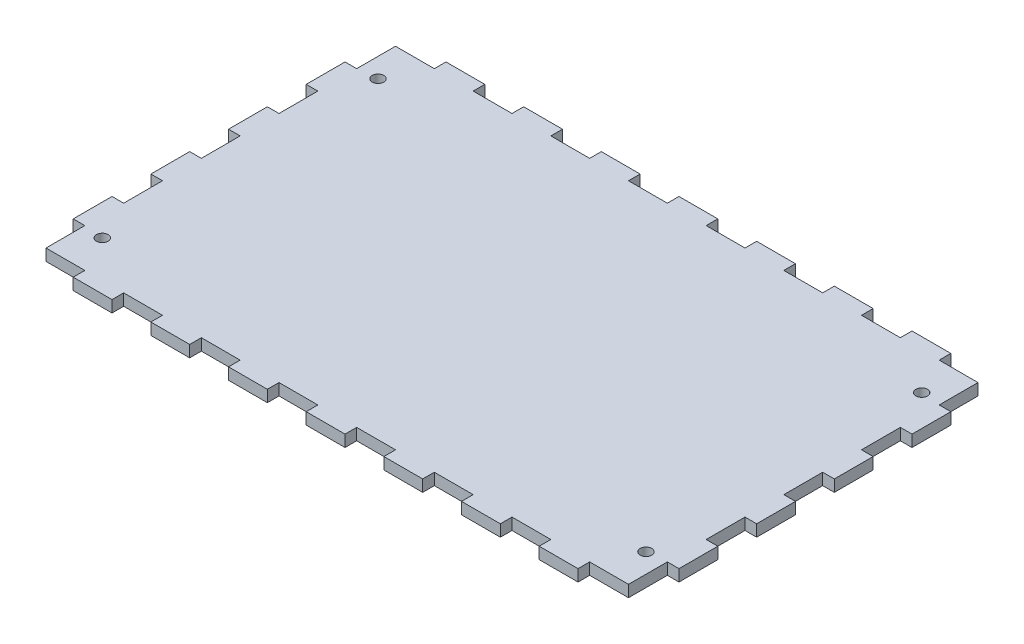
SolidWorks part; units mm, degrees
ref_plane "Front Plane" through (0, 0, 0) normal (0, 0, 1) x (1, 0, 0)
ref_plane "Top Plane" through (0, 0, 0) normal (0, 1, 0) x (1, 0, 0)
ref_plane "Right Plane" through (0, 0, 0) normal (1, 0, 0) x (0, 0, -1)
sketch "Sketch1" plane through (0, 0, 0) normal (0, 1, 0) x (1, 0, 0)
  line L0 (15, 45) -> (25, 48) construction
  line L1 (-76.5, 46.5) -> (76.5, 46.5) construction
  line L2 (-76.5, 46.5) -> (-76.5, -46.5) construction
  line L3 (-76.5, -46.5) -> (76.5, -46.5) construction
  line L4 (76.5, 46.5) -> (76.5, -46.5) construction
  line L5 (-76.5, 46.5) -> (76.5, -46.5) construction
  line L6 (-76.5, -46.5) -> (76.5, 46.5) construction
  line L7 (-5, 48) -> (5, 48)
  line L8 (-5, 48) -> (-5, 45)
  line L9 (-5, 45) -> (5, 45) construction
  line L10 (5, 48) -> (5, 45)
  line L11 (-5, 48) -> (5, 45) construction
  line L12 (-5, 45) -> (5, 48) construction
  line L13 (15, 45) -> (25, 45) construction
  line L14 (15, 48) -> (25, 45) construction
  line L15 (25, 48) -> (25, 45)
  line L16 (15, 48) -> (25, 48)
  line L17 (15, 48) -> (15, 45)
  line L18 (35, 45) -> (45, 48) construction
  line L19 (35, 45) -> (45, 45) construction
  line L20 (35, 48) -> (45, 45) construction
  line L21 (45, 48) -> (45, 45)
  line L22 (35, 48) -> (45, 48)
  line L23 (35, 48) -> (35, 45)
  line L24 (55, 45) -> (65, 48) construction
  line L25 (55, 45) -> (65, 45) construction
  line L26 (55, 48) -> (65, 45) construction
  line L27 (65, 48) -> (65, 45)
  line L28 (55, 48) -> (65, 48)
  line L29 (55, 48) -> (55, 45)
  line L30 (-25, 45) -> (-15, 48) construction
  line L31 (-25, 45) -> (-15, 45) construction
  line L32 (-25, 48) -> (-15, 45) construction
  line L33 (-15, 48) -> (-15, 45)
  line L34 (-25, 48) -> (-15, 48)
  line L35 (-25, 48) -> (-25, 45)
  line L36 (-45, 45) -> (-35, 48) construction
  line L37 (-45, 45) -> (-35, 45) construction
  line L38 (-45, 48) -> (-35, 45) construction
  line L39 (-35, 48) -> (-35, 45)
  line L40 (-45, 48) -> (-35, 48)
  line L41 (-45, 48) -> (-45, 45)
  line L42 (-65, 45) -> (-55, 48) construction
  line L43 (-65, 45) -> (-55, 45) construction
  line L44 (-65, 48) -> (-55, 45) construction
  line L45 (-55, 48) -> (-55, 45)
  line L46 (-65, 48) -> (-55, 48)
  line L47 (-65, 48) -> (-65, 45)
  line L48 (-55, 45) -> (-45, 45)
  line L49 (-35, 45) -> (-25, 45)
  line L50 (-15, 45) -> (-5, 45)
  line L51 (5, 45) -> (15, 45)
  line L52 (25, 45) -> (35, 45)
  line L53 (45, 45) -> (55, 45)
  line L54 (55, 48) -> (45, 48) construction
  line L55 (0, 0) -> (9.7796, 0) construction
  line L56 (0, 0) -> (0, 12.2502) construction
  line L57 (65, -48) -> (65, -45)
  line L58 (55, -48) -> (65, -48)
  line L59 (55, -48) -> (55, -45)
  line L60 (45, -45) -> (55, -45)
  line L61 (45, -48) -> (45, -45)
  line L62 (35, -48) -> (45, -48)
  line L63 (35, -48) -> (35, -45)
  line L64 (25, -45) -> (35, -45)
  line L65 (25, -48) -> (25, -45)
  line L66 (15, -48) -> (25, -48)
  line L67 (15, -48) -> (15, -45)
  line L68 (5, -45) -> (15, -45)
  line L69 (5, -48) -> (5, -45)
  line L70 (-5, -48) -> (5, -48)
  line L71 (-5, -48) -> (-5, -45)
  line L72 (-15, -45) -> (-5, -45)
  line L73 (-15, -48) -> (-15, -45)
  line L74 (-25, -48) -> (-15, -48)
  line L75 (-25, -48) -> (-25, -45)
  line L76 (-35, -45) -> (-25, -45)
  line L77 (-35, -48) -> (-35, -45)
  line L78 (-45, -48) -> (-35, -48)
  line L79 (-45, -48) -> (-45, -45)
  line L80 (-55, -45) -> (-45, -45)
  line L81 (-55, -48) -> (-55, -45)
  line L82 (-65, -48) -> (-65, -45)
  line L83 (-65, -48) -> (-55, -48)
  line L84 (-65, 45) -> (-75, 45)
  line L89 (-75, 45) -> (-75, 35)
  line L90 (-75, 25) -> (-75, 15)
  line L91 (-78, 25) -> (-75, 25)
  line L92 (-78, 25) -> (-78, 35)
  line L93 (-78, 35) -> (-75, 35)
  line L94 (-75, 25) -> (-75, 35) construction
  line L95 (-78, 25) -> (-75, 35) construction
  line L96 (-78, 35) -> (-75, 25) construction
  line L97 (-78, 5) -> (-75, 5)
  line L98 (-78, 5) -> (-75, 15) construction
  line L99 (-78, 5) -> (-78, 15)
  line L100 (-78, 15) -> (-75, 5) construction
  line L101 (-78, 15) -> (-75, 15)
  line L102 (-75, 5) -> (-75, 15) construction
  line L103 (-78, -15) -> (-75, -15)
  line L104 (-78, -15) -> (-75, -5) construction
  line L105 (-78, -15) -> (-78, -5)
  line L106 (-78, -5) -> (-75, -15) construction
  line L107 (-78, -5) -> (-75, -5)
  line L108 (-75, -15) -> (-75, -5) construction
  line L109 (-78, -35) -> (-75, -35)
  line L110 (-78, -35) -> (-75, -25) construction
  line L111 (-78, -35) -> (-78, -25)
  line L112 (-78, -25) -> (-75, -35) construction
  line L113 (-78, -25) -> (-75, -25)
  line L114 (-75, -35) -> (-75, -25) construction
  line L115 (-75, 5) -> (-75, -5)
  line L116 (-75, -15) -> (-75, -25)
  line L117 (-75, -35) -> (-75, -45)
  line L118 (-75, -45) -> (-65, -45)
  line L119 (65, 45) -> (75, 45)
  line L120 (65, -45) -> (75, -45)
  line L121 (75, -35) -> (75, -45)
  line L122 (78, -35) -> (75, -35)
  line L123 (78, -35) -> (78, -25)
  line L124 (78, -25) -> (75, -25)
  line L125 (75, -15) -> (75, -25)
  line L126 (78, -15) -> (75, -15)
  line L127 (78, -15) -> (78, -5)
  line L128 (78, -5) -> (75, -5)
  line L129 (75, 5) -> (75, -5)
  line L130 (78, 5) -> (75, 5)
  line L131 (78, 5) -> (78, 15)
  line L132 (78, 15) -> (75, 15)
  line L133 (75, 25) -> (75, 15)
  line L134 (78, 25) -> (75, 25)
  line L135 (78, 25) -> (78, 35)
  line L136 (78, 35) -> (75, 35)
  line L137 (75, 45) -> (75, 35)
  point P0 (0, 0)
  point P6 (0, 46.5)
  point P66 (-76.5, 30)
  dimension "D1" = 153
  dimension "D2" = 93
  dimension "D3" = 10
  dimension "D4" = 3
  dimension "D5" = 4
  dimension "D7" = 10
  dimension "D8" = 10
  dimension "D9" = 10
  dimension "D10" = 10
  dimension "D11" = 10
  dimension "D12" = 10
  dimension "D6" = 4
  dimension "D13" = 4
extrude "Boss-Extrude1" add sketch "Sketch1" along normal blind 3
sketch "Sketch2" plane through (0, 3, 0) normal (0, 1, 0) x (1, 0, 0)
  line L0 (0, 0) -> (0, 17.6247) construction
  line L1 (0, 0) -> (15.2388, 0) construction
  circle A0 centre (70, 35.5) radius 1.5
  circle A1 centre (-70, 35.5) radius 1.5
  circle A2 centre (70, -35.5) radius 1.5
  circle A3 centre (-70, -35.5) radius 1.5
  dimension "D3" = 3
  dimension "D1" = 70
  dimension "D2" = 35.5
extrude "Cut-Extrude1" cut sketch "Sketch2" against normal blind 3
